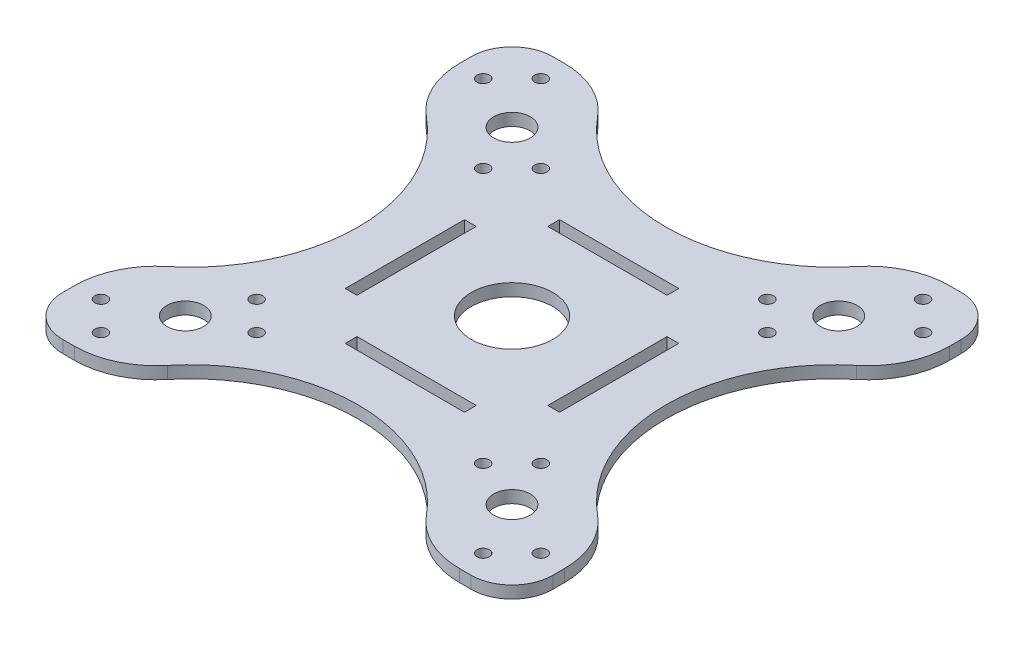
SolidWorks part; units mm, degrees
note: '?' marks a value the reader was unsure of.
ref_plane "Front" through (0, 0, 0) normal (0, 0, 1) x (1, 0, 0)
ref_plane "Top" through (0, 0, 0) normal (0, 1, 0) x (1, 0, 0)
ref_plane "Right" through (0, 0, 0) normal (1, 0, 0) x (0, 0, -1)
sketch "草图1" plane through (0, 0, 0) normal (0, 1, 0) x (1, 0, 0)
  line L0 (0, 24.7487) -> (0, 0) construction
  line L1 (60.1041, -60.1041) -> (36.5837, -60.1041)
  line L2 (60.1041, -60.1041) -> (60.1041, -36.5837)
  line L3 (60.1041, 60.1041) -> (36.5837, 60.1041)
  line L4 (-60.1041, -60.1041) -> (-60.1041, -36.5837)
  line L5 (60.1041, -60.1041) -> (-60.1041, 60.1041) construction
  line L6 (60.1041, 60.1041) -> (-60.1041, -60.1041) construction
  line L7 (0, 24.7487) -> (0, 78.8715) construction
  line L8 (-60.1041, 36.5837) -> (-60.1041, 60.1041)
  line L9 (60.1041, 36.5837) -> (60.1041, 60.1041)
  line L10 (-36.5837, -60.1041) -> (-60.1041, -60.1041)
  line L11 (-36.5837, 60.1041) -> (-60.1041, 60.1041)
  arc A0 (-36.5837, 60.1041) -> (36.5837, 60.1041) centre (0, 78.8715) ccw
  arc A1 (60.1041, 36.5837) -> (60.1041, -36.5837) centre (78.8715, 0) ccw
  arc A2 (36.5837, -60.1041) -> (-36.5837, -60.1041) centre (0, -78.8715) ccw
  arc A3 (-60.1041, -36.5837) -> (-60.1041, 36.5837) centre (-78.8715, 0) ccw
  point P0 (0, 0)
  point P23 (0, 0)
  dimension "D1" = 4
extrude "凸台-拉伸1" add sketch "草图1" along normal blind 3
fillet "圆角1" radius 10 1 edges at (60.1041, 1.5, 60.1041)
ref_axis "基准轴1" through (0, 27.9421, 0) along (0, 1, 0)?
fillet "圆角2" radius 10 1 edges at (60.1041, 1.5, -60.1041)
fillet "圆角3" radius 10 1 edges at (-60.1041, 1.5, -60.1041)
fillet "圆角4" radius 10 1 edges at (-60.1041, 1.5, 60.1041)
sketch "草图2" plane through (0, 3, 0) normal (0, 1, 0) x (1, 0, 0)
  line L0 (-60.1041, 36.5837) -> (-36.5837, 60.1041) construction
  line L1 (36.5837, -60.1041) -> (60.1041, -36.5837) construction
  line L2 (48.3439, -48.3439) -> (-48.3439, 48.3439) construction
  line L3 (-40.0733, 40.0733) -> (-36.5837, 60.1041) construction
  line L4 (-40.0733, 40.0733) -> (-60.1041, 36.5837) construction
  line L5 (-60.1041, 36.5837) -> (-48.3439, 48.3439) construction
  line L6 (-34.8639, 27.7928) -> (-27.7928, 34.8639) construction
  line L7 (36.5837, 60.1041) -> (-36.5837, 60.1041) construction
  line L12 (0, 60.1041) -> (0, 0) construction
  line L13 (-40.0733, 40.0733) -> (60.1041, 36.5837) construction
  line L14 (-50.7807, 30.9679) -> (-32.266, 49.4825) construction
  line L15 (14.6277, 26.2914) -> (-14.6277, 26.2914)
  line L16 (14.6277, 26.2914) -> (14.6277, 23.4038)
  line L17 (14.6277, 23.4038) -> (-14.6277, 23.4038)
  line L18 (-14.6277, 26.2914) -> (-14.6277, 23.4038)
  line L19 (14.6277, 26.2914) -> (-14.6277, 23.4038) construction
  line L20 (14.6277, 23.4038) -> (-14.6277, 26.2914) construction
  line L21 (-27.7928, 34.8639) -> (-46.8847, 53.9557) construction
  circle A0 centre (-27.7928, 34.8639) radius 1.52
  circle A1 centre (-34.8639, 27.7928) radius 1.52
  circle A2 centre (-40.0733, 40.0733) radius 4.5
  circle A3 centre (-46.8847, 53.9557) radius 1.52
  circle A4 centre (-53.9557, 46.8847) radius 1.52
  point P11 (-31.3283, 31.3283)
  point P19 (0, 24.8476)
extrude "切除-拉伸1" cut sketch "草图2" against normal blind 49
fillet "圆角5" radius 20 1 edges at (-36.5837, 1.5, -60.1041)
fillet "圆角6" radius 20 1 edges at (-60.1041, 1.5, -36.5837)
pattern_circular "阵列(圆周)2" count 4 every 90 about axis through (0, 0, 0) along (0, 1, 0) of "切除-拉伸1"
sketch "草图3" plane through (0, 3, 0) normal (0, 1, 0) x (1, 0, 0)
  circle A0 centre (0, 0) radius 10
extrude "切除-拉伸2" cut sketch "草图3" against normal blind 49
sketch "草图4" plane through (0, 3, 0) normal (0, 1, 0) x (1, 0, 0)
fillet "圆角7" radius 20 1 edges at (60.1041, 1.5, 36.5837)
fillet "圆角8" radius 20 1 edges at (36.5837, 1.5, 60.1041)
fillet "圆角9" radius 20 1 edges at (-60.1041, 1.5, 36.5837)
fillet "圆角10" radius 20 1 edges at (-36.5837, 1.5, 60.1041)
fillet "圆角11" radius 20 1 edges at (36.5837, 1.5, -60.1041)
fillet "圆角12" radius 20 1 edges at (60.1041, 1.5, -36.5837)
